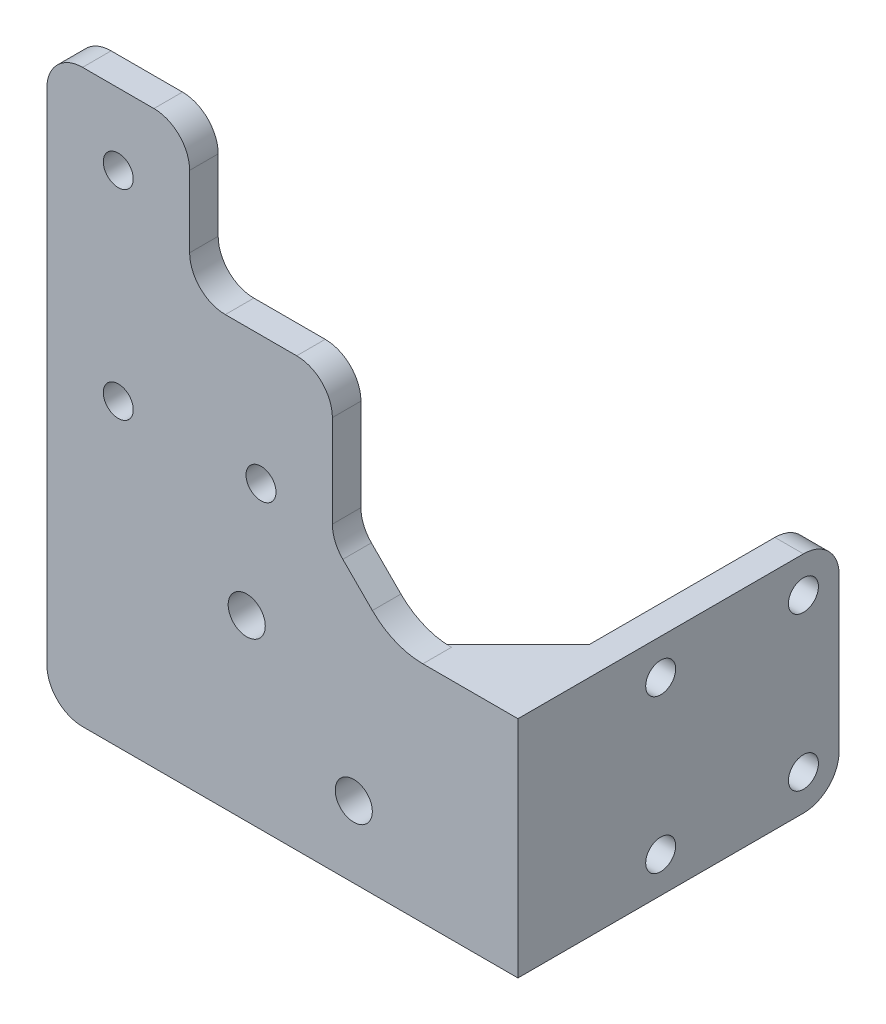
SolidWorks part; units mm, degrees
ref_plane "Спереди" through (0, 0, 0) normal (0, 0, 1) x (1, 0, 0)
ref_plane "Сверху" through (0, 0, 0) normal (0, 1, 0) x (1, 0, 0)
ref_plane "Справа" through (0, 0, 0) normal (1, 0, 0) x (0, 0, -1)
sketch "Model" plane through (0, 0, 0) normal (0, 0, 1) x (1, 0, 0)
  line L92 (308.3927, 233.3937) -> (308.3927, 210.4648)
  line L93 (303.3927, 205.4648) -> (263.3927, 205.4648)
  line L94 (258.3928, 210.4648) -> (258.3928, 280.4647)
  line L95 (263.3927, 285.4647) -> (273.3927, 285.4647)
  line L96 (278.3927, 280.4647) -> (278.3927, 270.4647)
  line L97 (283.3927, 265.4647) -> (293.3927, 265.4647)
  line L98 (298.3927, 260.4647) -> (298.3927, 247.5358)
  line L99 (299.8571, 244.0003) -> (306.9282, 236.9292)
  circle A59 centre (286.3927, 230.4648) radius 2.6
  circle A60 centre (301.3927, 215.4648) radius 2.6
  circle A61 centre (268.3927, 275.4647) radius 2.1
  circle A62 centre (268.3927, 247.4648) radius 2.1
  circle A63 centre (288.3927, 247.4648) radius 2.1
  arc A173 (303.3927, 205.4648) -> (308.3927, 210.4648) centre (303.3927, 210.4648) ccw
  arc A174 (258.3928, 210.4648) -> (263.3927, 205.4648) centre (263.3927, 210.4648) ccw
  arc A175 (263.3927, 285.4647) -> (258.3928, 280.4647) centre (263.3927, 280.4647) ccw
  arc A176 (278.3927, 280.4647) -> (273.3927, 285.4647) centre (273.3927, 280.4647) ccw
  arc A177 (278.3927, 270.4647) -> (283.3927, 265.4647) centre (283.3927, 270.4647) ccw
  arc A178 (298.3927, 260.4647) -> (293.3927, 265.4647) centre (293.3927, 260.4647) ccw
  arc A179 (298.3927, 247.5358) -> (299.8571, 244.0003) centre (303.3927, 247.5358) ccw
  arc A180 (308.3927, 233.3937) -> (306.9282, 236.9292) centre (303.3927, 233.3937) ccw
extrude "Бобышка-Вытянуть1" add sketch "Model" along normal blind 4
sketch "Эскиз1" plane through (0, 0, 0) normal (0, 0, -1) x (-1, 0, 0)
  line L0 (-303.3927, 205.4648) -> (-308.3927, 205.4648) construction
  line L1 (-308.3927, 205.4648) -> (-308.3927, 210.4648) construction
  line L2 (-308.3927, 233.3937) -> (-308.3927, 236.9292) construction
  line L3 (-308.3927, 236.9292) -> (-306.9282, 236.9292) construction
  line L4 (-308.3927, 232.6159) -> (-308.3927, 210.4648)
  line L5 (-308.3927, 236.9292) -> (-320.3927, 236.9292)
  line L6 (-308.3927, 233.3937) -> (-308.3927, 232.6159)
  line L7 (-308.3927, 205.4648) -> (-320.3927, 205.4648)
  line L8 (-320.3927, 236.9292) -> (-320.3927, 205.4648)
  line L9 (-308.3927, 236.9292) -> (-303.3927, 236.9292)
  line L10 (-308.3927, 233.3937) -> (-308.3927, 232.6159)
  line L11 (-308.3927, 232.6159) -> (-303.3927, 232.6159)
  line L12 (-303.3927, 236.9292) -> (-303.3927, 232.6159)
  line L13 (-308.3927, 205.4648) -> (-300.2108, 205.4648)
  line L15 (-308.3927, 210.4648) -> (-300.2108, 210.4648)
  line L16 (-300.2108, 205.4648) -> (-300.2108, 210.4648)
  arc M10 (-308.3927, 210.4648) -> (-303.3927, 205.4648) centre (-303.3927, 210.4648) ccw
  arc M24 (-306.9282, 236.9292) -> (-308.3927, 233.3937) centre (-303.3927, 233.3937) ccw
  line M25 (-308.3927, 233.3937) -> (-308.3927, 210.4648)
  dimension "D1" = 12
extrude "Бобышка-Вытянуть2" add sketch "Эскиз1" against normal blind 4 contours L7 L13 L9 L5 L8 M10 M25 M24 region at (314.2665, 221.0554, 0)
fillet "Скругление1" radius 10 1 edges at (306.9282, 236.9292, 2)
sketch "Эскиз4" plane through (320.3927, 0, 0) normal (1, 0, 0) x (0, 0, -1)
  line L1 (-4, 236.9292) -> (36, 236.9292)
  line L2 (-4, 236.9292) -> (-4, 205.4648)
  line L3 (-4, 205.4648) -> (36, 205.4648)
  line L4 (41, 231.9292) -> (41, 210.4648)
  line L7 (-4, 205.4648) -> (0, 205.4648) construction
  arc A0 (36, 205.4648) -> (41, 210.4648) centre (36, 210.4648) ccw
  arc A1 (41, 231.9292) -> (36, 236.9292) centre (36, 231.9292) ccw
  circle A2 centre (36, 231.9292) radius 2.1
  circle A3 centre (36, 210.4648) radius 2.1
  circle A4 centre (16, 231.9292) radius 2.1
  circle A5 centre (16, 210.4648) radius 2.1
  point P11 (41, 236.9292)
  dimension "D2" = 5
  dimension "D3" = 4.2
  dimension "D4" = 4.2
  dimension "D1" = 45
extrude "Бобышка-Вытянуть3" add sketch "Эскиз4" along normal blind 4
sketch "Эскиз5" plane through (0, 236.9292, 0) normal (0, 1, 0) x (1, 0, 0)
  line L0 (320.3927, 0) -> (320.3927, 10)
  line L1 (320.3927, 36) -> (320.3927, 0) construction
  line L2 (320.3927, 10) -> (310.3927, 0)
  line L3 (320.3927, 0) -> (311.0703, 0) construction
  line L4 (310.3927, 0) -> (320.3927, 0)
  dimension "D1" = 10
  dimension "D2" = 10
extrude "Бобышка-Вытянуть4" add sketch "Эскиз5" against normal blind 4
ref_plane "Плоскость1" through (0, 221.197, 0) normal (0, 1, 0) x (1, 0, 0)
mirror "Зеркальное отражение1" about plane through (0, 221.197, 0) normal (0, 1, 0) of "Бобышка-Вытянуть4"
